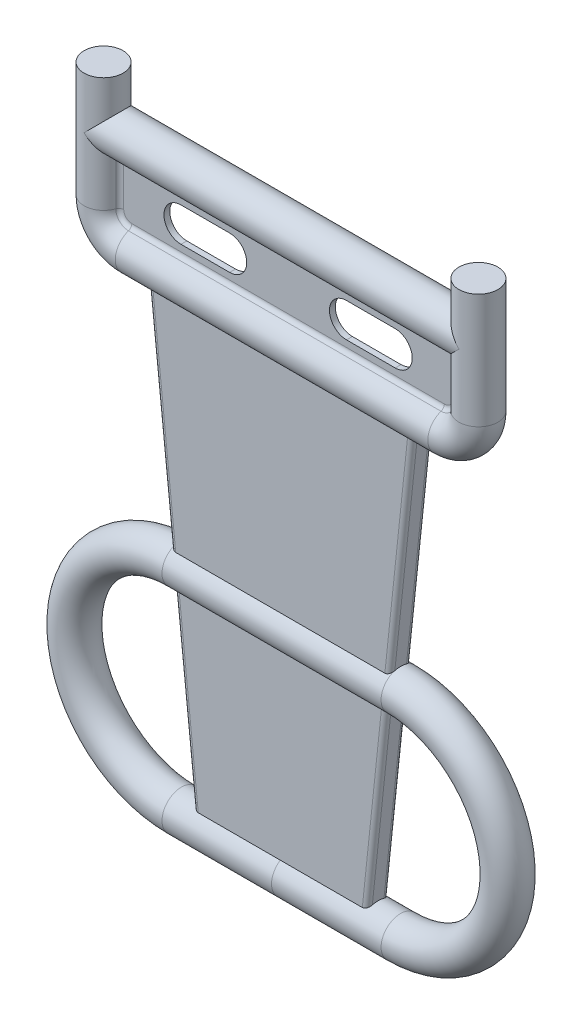
SolidWorks part; units mm, degrees
ref_plane "Front Plane" through (0, 0, 0) normal (0, 0, 1) x (1, 0, 0)
ref_plane "Top Plane" through (0, 0, 0) normal (0, 1, 0) x (1, 0, 0)
ref_plane "Right Plane" through (0, 0, 0) normal (1, 0, 0) x (0, 0, -1)
sketch "Sketch1" plane through (0, 0, 0) normal (0, 0, 1) x (1, 0, 0)
  line L0 (60, -0.5) -> (110, -0.5) construction
  line L1 (-192.5, 48.5) -> (192.5, 48.5)
  line L2 (-192.5, 48.5) -> (-192.5, -48.5)
  line L3 (-192.5, -48.5) -> (192.5, -48.5)
  line L4 (192.5, 48.5) -> (192.5, -48.5)
  line L5 (-192.5, 48.5) -> (192.5, -48.5) construction
  line L6 (-192.5, -48.5) -> (192.5, 48.5) construction
  line L7 (60, 17) -> (110, 17)
  line L8 (60, -18) -> (110, -18)
  line L9 (0, 0) -> (0, 66.6551) construction
  line L10 (-60, -0.5) -> (-110, -0.5) construction
  line L11 (-60, 17) -> (-110, 17)
  line L12 (-60, -18) -> (-110, -18)
  arc A0 (60, 17) -> (60, -18) centre (60, -0.5) ccw
  arc A1 (110, -18) -> (110, 17) centre (110, -0.5) ccw
  arc A2 (-60, 17) -> (-60, -18) centre (-60, -0.5) cw
  arc A3 (-110, -18) -> (-110, 17) centre (-110, -0.5) cw
  point P0 (0, 0)
  point P8 (85, -0.5)
  point P17 (-85, -0.5)
  point P22 (0, 0)
  point P23 (0, 0)
  point P24 (0, 0)
  point P25 (0, 0)
  point P26 (0, 0)
  point P27 (85, 0)
  point P28 (0, 0)
  point P29 (0, 0)
  point P30 (85, 0)
  point P31 (0, 0)
  point P32 (0, 0)
  dimension "D3" = 50
  dimension "D1" = 385
  dimension "D2" = 97
  dimension "D4" = 35
  dimension "D5" = 120
  dimension "D6" = 48
extrude "Boss-Extrude1" add sketch "Sketch1" along normal mid plane 6
sketch "Sketch2" plane through (0, 0, 0) normal (0, 0, 1) x (1, 0, 0)
  line L0 (0, 0) -> (0, -85.7384) construction
  line L1 (-137.5, -48.5) -> (-87.5, -523.5)
  line L2 (-192.5, -48.5) -> (192.5, -48.5) construction
  line L3 (-87.5, -523.5) -> (87.5, -523.5)
  line L4 (87.5, -523.5) -> (137.5, -48.5)
  line L5 (-137.5, -48.5) -> (137.5, -48.5)
  dimension "D1" = 275
  dimension "D2" = 175
  dimension "D3" = 475
extrude "Boss-Extrude2" add sketch "Sketch2" along normal mid plane 22
sketch "Sketch3" plane through (0, 0, 0) normal (0, 0, 1) x (1, 0, 0)
  line L0 (-160.5, -48.5) -> (160.5, -48.5)
  line L2 (192.5, -16.5) -> (192.5, 101.5)
  line L3 (0, 0) -> (0, 82.3053) construction
  line L4 (-192.5, -16.5) -> (-192.5, 101.5)
  line L5 (-137.5, -48.5) -> (137.5, -48.5) construction
  arc A0 (-160.5, -48.5) -> (-192.5, -16.5) centre (-160.5, -16.5) cw
  arc A1 (160.5, -48.5) -> (192.5, -16.5) centre (160.5, -16.5) ccw
  point P5 (0, -48.5)
  point P14 (-192.5, -48.5)
  point P17 (192.5, -48.5)
  dimension "D3" = 32
  dimension "D1" = 385
  dimension "D2" = 150
sketch "Sketch5" plane through (0, 0, 0) normal (0, 0, 1) x (1, 0, 0)
  line L0 (0, -523.5) -> (0, -365.5091) construction
  line L1 (-87.5, -523.5) -> (87.5, -523.5) construction
  line L2 (112.5, -523.5) -> (-112.5, -523.5)
  line L3 (-112.5, -303.5) -> (112.5, -303.5)
  arc A0 (112.5, -523.5) -> (112.5, -303.5) centre (112.5, -413.5) ccw
  arc A1 (-112.5, -523.5) -> (-112.5, -303.5) centre (-112.5, -413.5) cw
  dimension "D1" = 220
  dimension "D2" = 225
sketch "Sketch6" plane through (0, 0, 0) normal (1, 0, 0) x (0, 0, -1)
  circle A0 centre (0, -48.5) radius 20
  point P9 (0, -531.1795)
  point P10 (0, 0)
  point P11 (0, -523.5)
  dimension "D1" = 40
sweep "Sweep1" add profiles "Sketch6" path "Sketch3"
sketch "Sketch7" plane through (0, 0, 0) normal (1, 0, 0) x (0, 0, -1)
  line L0 (-11, -523.5) -> (11, -523.5) construction
  circle A0 centre (0, -523.5) radius 20
  dimension "D1" = 40
sweep "Sweep2" add profiles "Sketch7" path "Sketch5"
sketch "Sketch8" plane through (0, 0, 0) normal (0, 0, 1) x (1, 0, 0)
  line L0 (-192.5, 48.5) -> (192.5, 48.5)
  line L1 (0, 48.5) -> (0, 0) construction
  line L2 (172.7263, 48.5) -> (-172.7263, 48.5) construction
  dimension "D1" = 385
sketch "Sketch9" plane through (0, 0, 0) normal (1, 0, 0) x (0, 0, -1)
  line L0 (0, 48.5) -> (0, 0) construction
  circle A0 centre (0, 48.5) radius 20
  circle A1 centre (0, -523.5) radius 20 construction
  dimension "D1" = 40
  dimension "D2" = 572
sweep "Sweep3" add profiles "Sketch9" path "Sketch8"
fillet "Fillet2" radius 5 12 edges at (-172.7263, 6.1131, -3) (-169.1453, -25.1453, -3) (169.1453, -25.1453, -3) (172.7263, 6.1131, -3) (0, 28.7263, -3) (0, -28.7263, -3) (169.1453, -25.1453, 3) (-169.1453, -25.1453, 3) (-172.7263, 6.1131, 3) (0, 28.7263, 3) (172.7263, 6.1131, 3) (0, -28.7263, 3)
fillet "Fillet3" radius 5 4 edges at (-124.0789, -176, -11) (124.0789, -176, -11) (-124.0789, -176, 11) (124.0789, -176, 11)
fillet "Fillet4" radius 5 4 edges at (-99.0789, -413.5, 11) (-99.0789, -413.5, -11) (99.0789, -413.5, -11) (99.0789, -413.5, 11)
